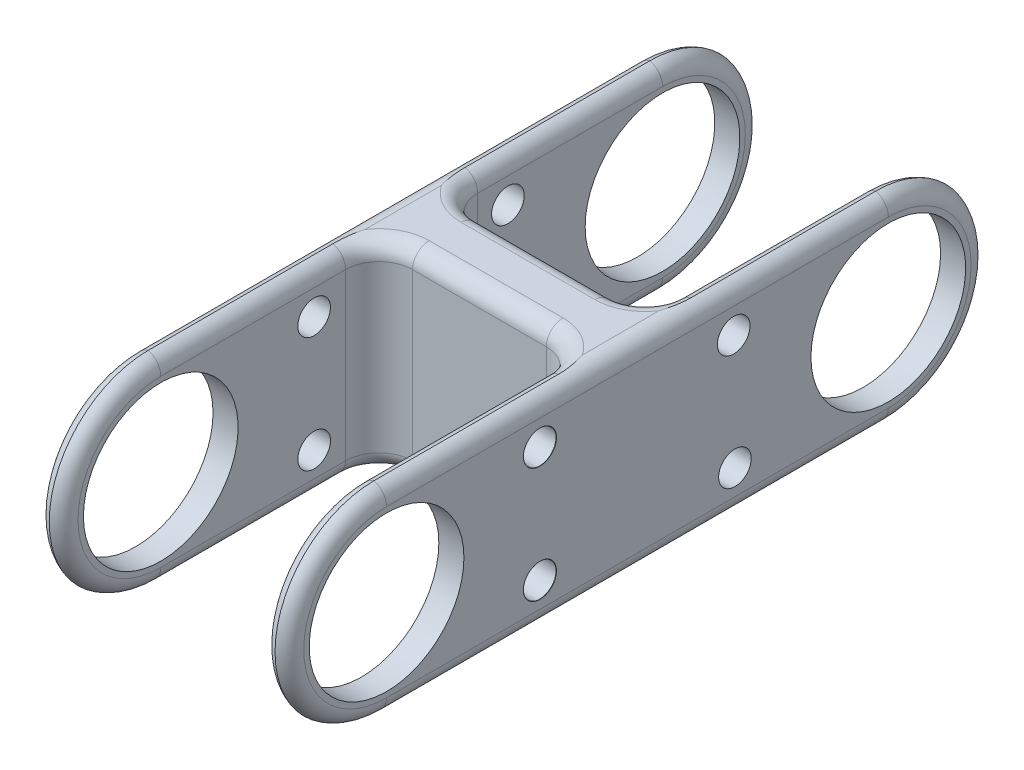
SolidWorks part; units mm, degrees
ref_plane "Front Plane" through (0, 0, 0) normal (0, 0, 1) x (1, 0, 0)
ref_plane "Top Plane" through (0, 0, 0) normal (0, 1, 0) x (1, 0, 0)
ref_plane "Right Plane" through (0, 0, 0) normal (1, 0, 0) x (0, 0, -1)
sketch "Sketch1" plane through (0, 0, 0) normal (1, 0, 0) x (0, 0, -1)
  line L0 (0, 11.9) -> (60, 11.9)
  line L1 (0, -11.9) -> (60, -11.9)
  line L2 (30, 11.9) -> (30, -11.9) construction
  circle A0 centre (0, 0) radius 9.25
  arc A1 (0, 11.9) -> (0, -11.9) centre (0, 0) ccw
  circle A2 centre (60, 0) radius 9.25
  arc A3 (60, 11.9) -> (60, -11.9) centre (60, 0) cw
  dimension "D1" = 18.5
  dimension "D2" = 23.8
  dimension "D3" = 60
extrude "Boss-Extrude1" add sketch "Sketch1" along normal blind 30
sketch "Sketch2" plane through (0, 11.9, 0) normal (0, 1, 0) x (1, 0, 0)
  line L0 (0, -11.9) -> (30, -11.9) construction
  line L1 (3, -11.9) -> (27, -11.9)
  line L2 (3, -11.9) -> (3, 26.1)
  line L3 (3, 26.1) -> (27, 26.1)
  line L4 (27, -11.9) -> (27, 26.1)
  line L5 (0, 30) -> (30, 30) construction
  line L6 (0, 60) -> (0, 0) construction
  line L7 (30, 60) -> (30, 0) construction
  line L8 (3, 33.9) -> (27, 33.9)
  line L9 (27, 71.9) -> (27, 33.9)
  line L10 (3, 71.9) -> (27, 71.9)
  line L11 (3, 71.9) -> (3, 33.9)
  dimension "D1" = 38
  dimension "D2" = 3
  dimension "D3" = 3
extrude "Cut-Extrude1" cut sketch "Sketch2" against normal through all
ref_plane "Plane1" through (0, 0, -30) normal (0, 0, 1) x (1, 0, 0)
fillet "Fillet1" radius 4 4 edges at (27, 0, -26.1) (3, 0, -26.1) (27, 0, -33.9) (3, 0, -33.9)
hole_wizard "M3.5 Clearance Hole1" positions "Sketch3" profile "Sketch4" hole size "M3.5" standard "ANSI Metric" end condition through all
sketch "Sketch3" plane through (0, 0, 0) normal (-1, 0, 0) x (0, 0, 1)
  circle A0 centre (-41.511, 6.9) radius 1.7024 construction
  point P0 (-41.66, -6.9)
  point P3 (-41.511, 6.9)
sketch "Sketch4" plane through (0, -6.9, -41.66) normal (0, 1, 0) x (0, 0, 1)
  line L0 (0, 0) -> (0, 30)
  line L1 (0, 30) -> (1.95, 30)
  line L2 (1.95, 30) -> (1.95, 0.025)
  line L3 (1.95, 0.025) -> (1.975, 0)
  line L5 (1.975, 0) -> (0, 0)
  line L6 (-1.95, 0.025) -> (-1.975, 0) construction
  line L11 (0, -6.35) -> (0, 107.95) construction
  dimension "Thru Hole Dia." = 3.9
  dimension "Thru Hole Depth" = 30
  dimension "Near C'Sink Dia." = 3.95
  dimension "Near C'Sink Angle" = 90
sketch "Sketch5" plane through (0, 0, -33.9) normal (0, 0, -1) x (-1, 0, 0)
  line L0 (-23, 11.9) -> (-23, -11.9) construction
  line L1 (-23, 0) -> (-7, 0) construction
  line L2 (-7, -11.9) -> (-7, 11.9) construction
  line B0 (-23, -3.65) -> (-23, -10.15)
  line B1 (-23, -3.65) -> (-20, -3.65)
  line B2 (-20, -3.65) -> (-20, -10.15)
  line B3 (-23, -10.15) -> (-20, -10.15)
  line B4 (-23, 0) -> (-7, 0) construction
  line B5 (-14.9675, -0.1255) -> (-15, -8.8352) construction
  line B6 (-7.01, -10.2096) -> (-10.0099, -10.1872)
  line B7 (-9.9615, -3.6874) -> (-10.0099, -10.1872)
  line B8 (-6.9616, -3.7098) -> (-9.9615, -3.6874)
  line B9 (-6.9616, -3.7098) -> (-7.01, -10.2096)
  line B10 (-6.9616, 3.7098) -> (-7.01, 10.2096)
  line B11 (-6.9616, 3.7098) -> (-9.9615, 3.6874)
  line B12 (-9.9615, 3.6874) -> (-10.0099, 10.1872)
  line B13 (-7.01, 10.2096) -> (-10.0099, 10.1872)
  line B14 (-23, 10.15) -> (-20, 10.15)
  line B15 (-20, 3.65) -> (-20, 10.15)
  line B16 (-23, 3.65) -> (-20, 3.65)
  line B17 (-23, 3.65) -> (-23, 10.15)
sketch_block_instance "Block1-1"
sketch_block "Block1" parameters "D1"=3, "D2"=6.5
sketch "Sketch6" plane through (30, 0, 0) normal (-1, 0, 0) x (0, 0, 1)
  line L0 (-39.685, -6.9) -> (-43.635, -6.9) construction
  circle A0 centre (-41.66, -6.9) radius 1.975 construction
hole_wizard "M3.5 Clearance Hole2" positions "Sketch9" profile "Sketch8" hole size "M3.5" standard "ANSI Metric" end condition through all
sketch "Sketch9" plane through (30, 0, 0) normal (1, 0, 0) x (0, 0, -1)
  point P0 (18.34, 6.9)
  point P3 (18.34, -6.9)
sketch "Sketch8" plane through (30, 6.9, -18.34) normal (0, 1, 0) x (0, 0, -1)
  line L0 (0, 0) -> (0, 30)
  line L1 (0, 30) -> (1.95, 30)
  line L2 (1.95, 30) -> (1.95, 0.025)
  line L3 (1.95, 0.025) -> (1.975, 0)
  line L5 (1.975, 0) -> (0, 0)
  line L6 (-1.95, 0.025) -> (-1.975, 0) construction
  line L11 (0, -6.35) -> (0, 107.95) construction
  dimension "Thru Hole Dia." = 3.9
  dimension "Thru Hole Depth" = 30
  dimension "Near C'Sink Dia." = 3.95
  dimension "Near C'Sink Angle" = 90
sketch "Sketch10" plane through (0, 0, -26.1) normal (0, 0, 1) x (1, 0, 0)
  line L0 (-1.0691, -12.5585) -> (14.9309, -12.5585) construction
  line L1 (23, 0) -> (7, 0) construction
  line L2 (23, -11.9) -> (23, 11.9) construction
  line L3 (7, 11.9) -> (7, -11.9) construction
  line B0 (7, -3.65) -> (7, -10.15)
  line B1 (7, -3.65) -> (10, -3.65)
  line B2 (10, -3.65) -> (10, -10.15)
  line B3 (7, -10.15) -> (10, -10.15)
  line B4 (7, 0) -> (23, 0) construction
  line B5 (22.99, -10.2096) -> (19.9901, -10.1872)
  line B6 (20.0385, -3.6874) -> (19.9901, -10.1872)
  line B7 (23.0384, -3.7098) -> (20.0385, -3.6874)
  line B8 (23.0384, -3.7098) -> (22.99, -10.2096)
  line B9 (23.0384, 3.7098) -> (22.99, 10.2096)
  line B10 (23.0384, 3.7098) -> (20.0385, 3.6874)
  line B11 (20.0385, 3.6874) -> (19.9901, 10.1872)
  line B12 (22.99, 10.2096) -> (19.9901, 10.1872)
  line B13 (7, 10.15) -> (10, 10.15)
  line B14 (10, 3.65) -> (10, 10.15)
  line B15 (7, 3.65) -> (10, 3.65)
  line B16 (7, 3.65) -> (7, 10.15)
sketch_block_instance "Block1-2"
fillet "Fillet2" [suppressed] radius 2
hole_wizard "M3.5 Clearance Hole3" positions "Sketch11" profile "Sketch12" hole size "M3.5" standard "ANSI Metric" end condition through all
sketch "Sketch11" plane through (30, 0, 0) normal (1, 0, 0) x (0, 0, -1)
  point P0 (18.34, 6.9)
  point P3 (18.34, -6.9)
sketch "Sketch12" plane through (30, 6.9, -18.34) normal (0, 1, 0) x (0, 0, -1)
  line L0 (0, 0) -> (0, 30)
  line L1 (0, 30) -> (1.95, 30)
  line L2 (1.95, 30) -> (1.95, 0.025)
  line L3 (1.95, 0.025) -> (1.975, 0)
  line L5 (1.975, 0) -> (0, 0)
  line L6 (-1.95, 0.025) -> (-1.975, 0) construction
  line L11 (0, -6.35) -> (0, 107.95) construction
  dimension "Thru Hole Dia." = 3.9
  dimension "Thru Hole Depth" = 30
  dimension "Near C'Sink Dia." = 3.95
  dimension "Near C'Sink Angle" = 90
sketch "Sketch13" [suppressed] plane through (0, 0, 0) normal (-1, 0, 0) x (0, 0, 1)
  line L0 (-125.6084, 9.9) -> (-125.6084, -9.9) construction
  line L1 (0, 9.9) -> (-60, 9.9) construction
  line L2 (-60, -9.9) -> (0, -9.9) construction
  point P0 (-128.6084, 6.9)
  dimension "D1" = 3
fillet "Fillet3" radius 2 32 edges at (0, 0, -71.9) (0, -11.9, -30) (0, 0, 11.9) (3, 0, -71.9) (3, -11.9, -48.95) (4.1716, -11.9, -35.0716) (15, -11.9, -33.9) (25.8284, -11.9, -35.0716) (27, -11.9, -48.95) (27, 0, -71.9) (30, 0, -71.9) (30, -11.9, -30) (30, 0, 11.9) (27, 0, 11.9) (27, -11.9, -11.05) (25.8284, -11.9, -24.9284) (15, -11.9, -26.1) (4.1716, -11.9, -24.9284) (3, -11.9, -11.05) (3, 0, 11.9) (0, 11.9, -30) (3, 11.9, -48.95) (4.1716, 11.9, -35.0716) (15, 11.9, -33.9) (25.8284, 11.9, -35.0716) (27, 11.9, -48.95) (30, 11.9, -30) (27, 11.9, -11.05) (25.8284, 11.9, -24.9284) (15, 11.9, -26.1) (4.1716, 11.9, -24.9284) (3, 11.9, -11.05)
